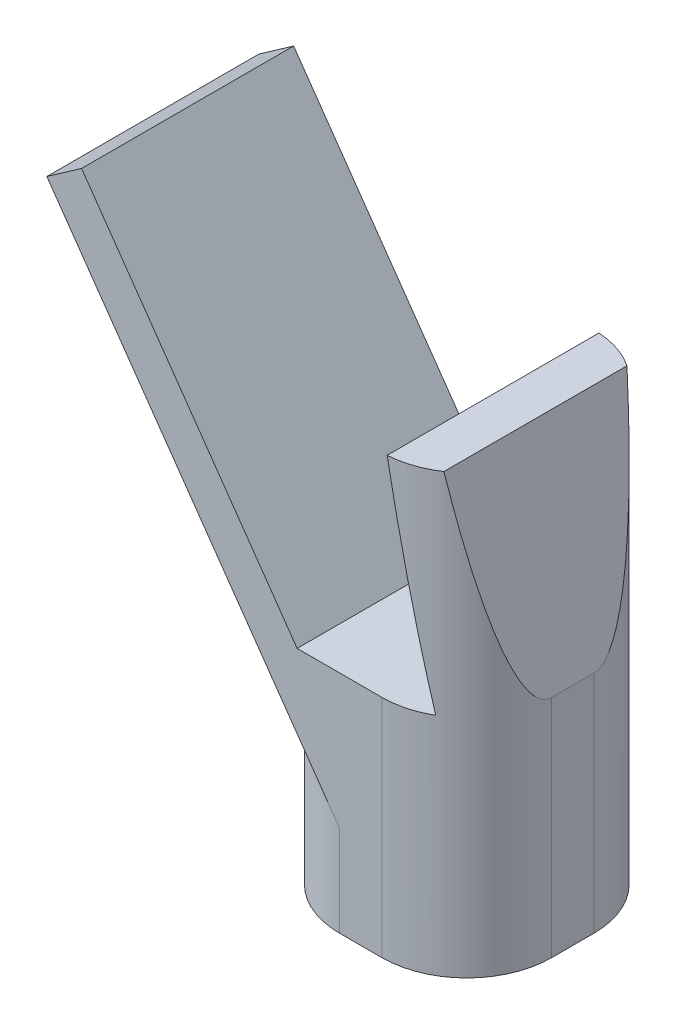
SolidWorks part; units mm, degrees
ref_plane "Front Plane" through (0, 0, 0) normal (0, 0, 1) x (1, 0, 0)
ref_plane "Top Plane" through (0, 0, 0) normal (0, 1, 0) x (1, 0, 0)
ref_plane "Right Plane" through (0, 0, 0) normal (1, 0, 0) x (0, 0, -1)
sketch "Sketch2" plane through (0, 0, 0) normal (0, 0, 1) x (1, 0, 0)
  line L0 (-10.16, 13.5009) -> (-2.54, 13.5009)
  line L1 (0, 0) -> (-12.7, 0)
  line L2 (-12.7, 0) -> (-12.7, 12.7)
  line L3 (-12.7, 12.7) -> (-25.1497, 30.48)
  line L4 (0, 13.5009) -> (0, 0)
  line L5 (-10.16, 13.5009) -> (-23.069, 31.9369)
  line L6 (-10.16, 2.54) -> (-10.16, 13.5009) construction
  line L7 (0, 2.54) -> (-10.16, 2.54) construction
  line L8 (-23.069, 31.9369) -> (-25.1497, 30.48)
  line L9 (0, 13.5009) -> (-2.2394, 26.2009)
  line L10 (-2.2394, 26.2009) -> (-4.7794, 26.2009)
  line L11 (-4.7794, 26.2009) -> (-2.54, 13.5009)
  dimension "D1" = 145
  dimension "D2" = 17.78
  dimension "D3" = 12.7
  dimension "D4" = 12.7
  dimension "D5" = 12.7
  dimension "D6" = 2.54
  dimension "D7" = 80
extrude "Boss-Extrude1" add sketch "Sketch2" along normal blind 12.7
fillet "Fillet2" radius 5.08 4 edges at (-12.7, 6.35, 12.7) (-12.7, 6.35, 0) (0, 6.7504, 0) (0, 6.7504, 12.7)
sketch "Sketch5" plane through (0, 0, 0) normal (0, -1, 0) x (1, 0, 0)
  line L0 (-6.35, 12.7) -> (-6.35, 0) construction
  line L1 (-7.62, 12.7) -> (-5.08, 12.7) construction
  line L2 (-7.62, 0) -> (-5.08, 0) construction
  circle A0 centre (-6.35, 6.35) radius 1.27
extrude "Cut-Extrude1" cut sketch "Sketch5" against normal through all both and the other way through all
